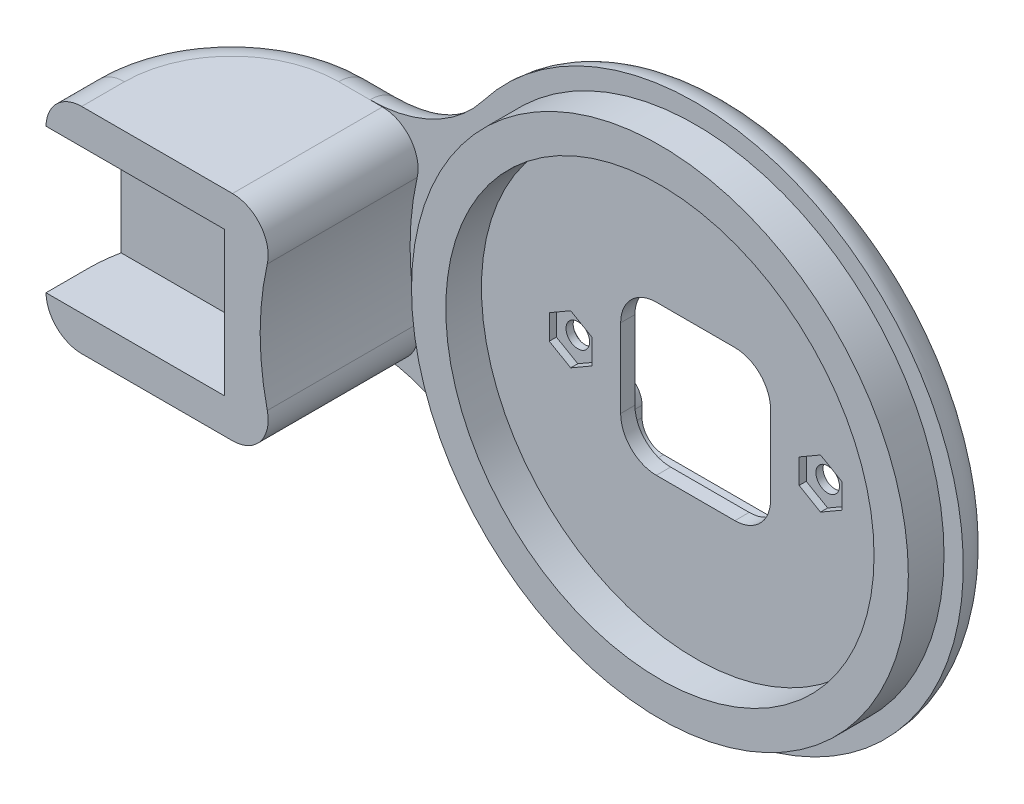
SolidWorks part; units mm, degrees
ref_plane "Plan de face" through (0, 0, 0) normal (0, 0, 1) x (1, 0, 0)
ref_plane "Plan de dessus" through (0, 0, 0) normal (0, 1, 0) x (1, 0, 0)
ref_plane "Plan de droite" through (0, 0, 0) normal (1, 0, 0) x (0, 0, -1)
sketch "Esquisse1" plane through (0, 0, 0) normal (0, 0, 1) x (1, 0, 0)
  line L0 (-1000, 0) -> (49000, 0) construction
  line L1 (-45.6207, 15) -> (-70, 15)
  line L4 (-70, -15) -> (-70, 15)
  line L5 (-45.6207, -15) -> (-70, -15)
  arc A0 (-29.7526, -22.8261) -> (-29.7526, 22.8261) centre (0, 0) ccw
  arc A2 (-45.6207, 15) -> (-29.7526, 22.8261) centre (-45.6207, 35) ccw
  arc A3 (-45.6207, -15) -> (-29.7526, -22.8261) centre (-45.6207, -35) cw
  point P8 (-34.3693, -15)
  point P9 (-70, 0)
  point P13 (-70, 0)
  point P20 (-34.3693, 15)
  dimension "D1" = 75
  dimension "D5" = 20
  dimension "D2" = 15
  dimension "D3" = 70
extrude "Boss.-Extru.1" add sketch "Esquisse1" along normal blind 5
sketch "Esquisse6" plane through (0, 0, 5) normal (0, 0, 1) x (1, 0, 0)
  circle A0 centre (0, 0) radius 34.8
  circle A1 centre (0, 0) radius 30
  dimension "D1" = 69.6
  dimension "D2" = 60
extrude "Boss.-Extru.6" add sketch "Esquisse6" along normal blind 5
sketch "Esquisse8" plane through (0, 0, 5) normal (0, 0, 1) x (1, 0, 0)
  line L1 (-1000, 0) -> (49000, 0) construction
  line L3 (-70, -15) -> (-70, 15)
  line L9 (-70, -15) -> (-43.8748, -15)
  line L10 (-70, 15) -> (-43.8748, 15)
  line L20 (-70, 15) -> (-70, -15) construction
  arc A2 (-38.9998, 8.8889) -> (-38.9998, -8.8889) centre (0, 0) ccw
  arc A3 (-43.8748, 15) -> (-38.9998, 8.8889) centre (-43.8748, 10) cw
  arc A4 (-43.8748, -15) -> (-38.9998, -8.8889) centre (-43.8748, -10) ccw
  point P5 (-70, 0)
  point P15 (-70, 0)
  dimension "D1" = 80
  dimension "D2" = 5
extrude "Boss.-Extru.9" add sketch "Esquisse8" along normal blind 21
fillet "Congé1" radius 20 1 edges at (-70, 0, 0)
fillet "Congé2" radius 5 9 edges at (-47.8104, -15, 0) (-36.7742, -17.0629, 0) (37.5, 0, 0) (-36.7742, 17.0629, 0) (-47.8104, 15, 0) (-64.1421, 15, 5.8579) (-64.1421, -15, 5.8579) (-70, -15, 23) (-70, 15, 23)
sketch "Esquisse11" plane through (-70, 0, 0) normal (-1, 0, 0) x (0, 0, 1)
  line L0 (26, 10) -> (20, 10) construction
  line L1 (16, 10) -> (36, 10) construction
  line L2 (16, 10) -> (16, -10) construction
  line L3 (16, -10) -> (36, -10) construction
  line L4 (36, 10) -> (36, -10) construction
  line L5 (20, -10) -> (26, -10) construction
  line L6 (0, -10) -> (0, 10) construction
  line L7 (15.9, 10.1) -> (36.1, 10.1)
  line L8 (36.1, 10.1) -> (36.1, -10.1)
  line L9 (15.9, -10.1) -> (36.1, -10.1)
  line L10 (15.9, 10.1) -> (15.9, -10.1)
  dimension "D1" = 16
  dimension "D2" = 20
  dimension "D3" = 0.1
extrude "Enlèv. mat.-Extru.2" cut sketch "Esquisse11" against normal blind 25
sketch "Esquisse12" plane through (0, 0, 15.9) normal (0, 0, 1) x (1, 0, 0)
  line L0 (-69.5752, 10) -> (-69.5752, -10) construction
  circle A0 centre (-49.5752, 0) radius 2.6
  dimension "D1" = 5.2
  dimension "D2" = 20
extrude "Enlèv. mat.-Extru.3" cut sketch "Esquisse12" against normal through all
sketch "Esquisse13" plane through (0, 0, 15.9) normal (0, 0, 1) x (1, 0, 0)
  circle A0 centre (-49.5752, 0) radius 4.5
  dimension "D1" = 9
extrude "Enlèv. mat.-Extru.4" cut sketch "Esquisse13" against normal through all from offset 5 offset against normal yes
sketch "Esquisse14" plane through (0, 0, 5) normal (0, 0, 1) x (1, 0, 0)
  line L6 (-5.5, 10.5) -> (5.5, 10.5)
  line L11 (-1000, 0) -> (49000, 0) construction
  line L16 (-10.5, 5.5) -> (-10.5, -5.5)
  line L17 (-5.5, -10.5) -> (5.5, -10.5)
  line L18 (10.5, 5.5) -> (10.5, -5.5)
  line L19 (-10.5, 10.5) -> (10.5, -10.5) construction
  line L20 (-10.5, -10.5) -> (10.5, 10.5) construction
  arc A8 (-10.5, -5.5) -> (-5.5, -10.5) centre (-5.5, -5.5) ccw
  arc A9 (5.5, -10.5) -> (10.5, -5.5) centre (5.5, -5.5) ccw
  arc A10 (5.5, 10.5) -> (10.5, 5.5) centre (5.5, 5.5) cw
  arc A11 (-5.5, 10.5) -> (-10.5, 5.5) centre (-5.5, 5.5) ccw
  point P0 (0, 0)
  dimension "D2" = 5
  dimension "D1" = 21
extrude "Enlèv. mat.-Extru.5" cut sketch "Esquisse14" against normal blind 2
sketch "Esquisse17" plane through (0, 0, 0) normal (0, 0, -1) x (-1, 0, 0)
  line L0 (15.5, 5) -> (19.5, 5)
  line L1 (-9.5, 12.5) -> (9.5, 12.5)
  line L3 (-9.5, -12.5) -> (9.5, -12.5)
  line L4 (12.5, 9.5) -> (12.5, 8)
  line L5 (12.5, -8) -> (12.5, -9.5)
  line L6 (0, -1000) -> (0, 49000) construction
  line L10 (22.5, -2) -> (22.5, 2)
  line L11 (-12.5, -8) -> (-12.5, -9.5)
  line L12 (-15.5, -5) -> (-19.5, -5)
  line L13 (-22.5, -2) -> (-22.5, 2)
  line L14 (-15.5, 5) -> (-19.5, 5)
  line L15 (15.5, -5) -> (19.5, -5)
  line L16 (-12.5, 9.5) -> (-12.5, 8)
  arc A0 (19.5, -5) -> (22.5, -2) centre (19.5, -2) ccw
  arc A1 (19.5, 5) -> (22.5, 2) centre (19.5, 2) cw
  arc A2 (15.5, 5) -> (12.5, 8) centre (15.5, 8) cw
  arc A3 (15.5, -5) -> (12.5, -8) centre (15.5, -8) ccw
  arc A4 (9.5, -12.5) -> (12.5, -9.5) centre (9.5, -9.5) ccw
  arc A5 (-12.5, -9.5) -> (-9.5, -12.5) centre (-9.5, -9.5) ccw
  arc A6 (9.5, 12.5) -> (12.5, 9.5) centre (9.5, 9.5) cw
  arc A7 (-9.5, 12.5) -> (-12.5, 9.5) centre (-9.5, 9.5) ccw
  arc A8 (-15.5, -5) -> (-12.5, -8) centre (-15.5, -8) cw
  arc A9 (-19.5, -5) -> (-22.5, -2) centre (-19.5, -2) cw
  arc A10 (-19.5, 5) -> (-22.5, 2) centre (-19.5, 2) ccw
  arc A11 (-15.5, 5) -> (-12.5, 8) centre (-15.5, 8) ccw
  point P0 (0, 0)
  point P6 (12.5, 0)
  point P13 (22.5, -5)
  point P16 (22.5, 5)
  point P21 (12.5, -5)
  point P28 (12.5, 12.5)
  point P31 (-12.5, 12.5)
  dimension "D4" = 3
  dimension "D1" = 25
  dimension "D2" = 10
  dimension "D3" = 10
extrude "Enlèv. mat.-Extru.7" cut sketch "Esquisse17" against normal blind 3
sketch "Esquisse19" plane through (0, 0, 3) normal (0, 0, -1) x (-1, 0, 0)
  line L0 (0, -1000) -> (0, 49000) construction
  line L1 (22.5, -2) -> (22.5, 2) construction
  circle A0 centre (17.5, 0) radius 1.65
  circle A1 centre (-17.5, 0) radius 1.65
  dimension "D2" = 3.3
  dimension "D1" = 5
extrude "Enlèv. mat.-Extru.8" cut sketch "Esquisse19" against normal through all
sketch "Esquisse20" plane through (0, 0, 5) normal (0, 0, 1) x (1, 0, 0)
  line L0 (0, -1000) -> (0, 49000) construction
  line L1 (-17.5, -3.4641) -> (-14.5, -1.7321)
  line L2 (-14.5, -1.7321) -> (-14.5, 1.7321)
  line L3 (-14.5, 1.7321) -> (-17.5, 3.4641)
  line L4 (-17.5, 3.4641) -> (-20.5, 1.7321)
  line L5 (-20.5, 1.7321) -> (-20.5, -1.7321)
  line L6 (-20.5, -1.7321) -> (-17.5, -3.4641)
  line L7 (20.5, -1.7321) -> (17.5, -3.4641)
  line L8 (20.5, 1.7321) -> (20.5, -1.7321)
  line L9 (17.5, 3.4641) -> (20.5, 1.7321)
  line L10 (14.5, 1.7321) -> (17.5, 3.4641)
  line L11 (14.5, -1.7321) -> (14.5, 1.7321)
  line L12 (17.5, -3.4641) -> (14.5, -1.7321)
  circle A0 centre (-17.5, 0) radius 3 construction
  dimension "D1" = 6
extrude "Enlèv. mat.-Extru.9" cut sketch "Esquisse20" against normal blind 1
